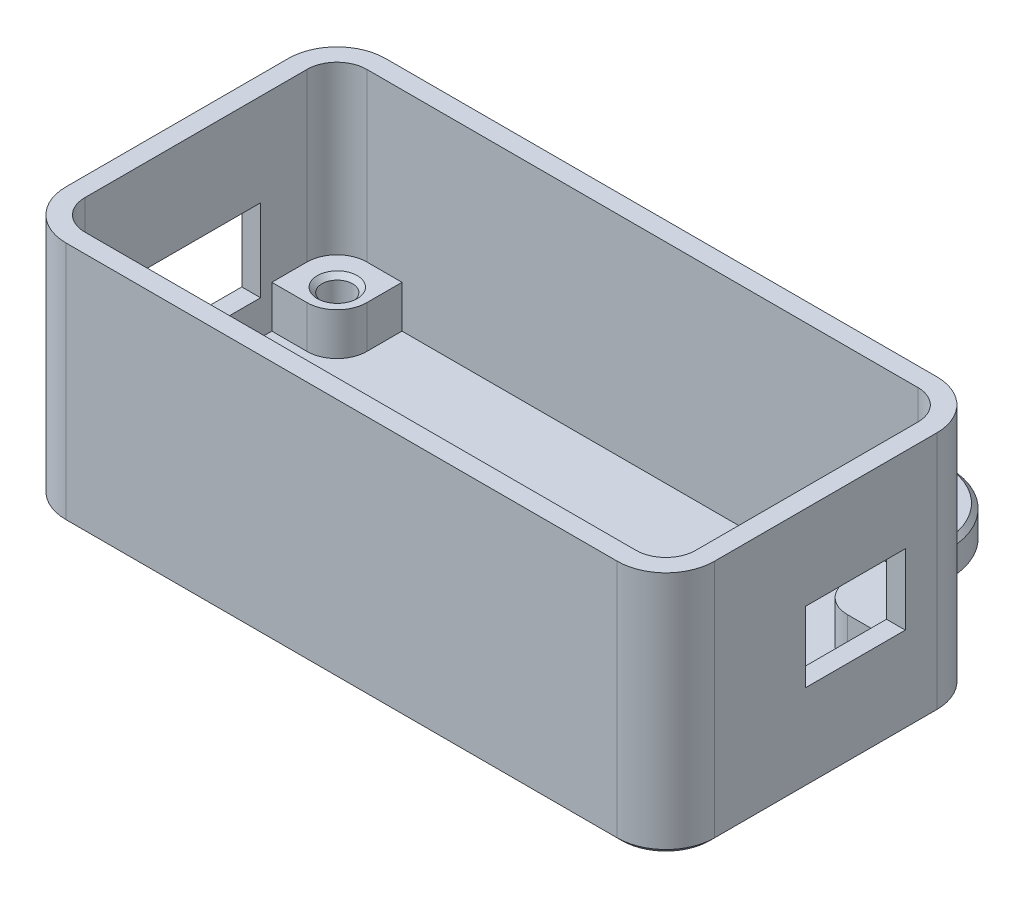
SolidWorks part; units mm, degrees
ref_plane "Front Plane" through (0, 0, 0) normal (0, 0, 1) x (1, 0, 0)
ref_plane "Top Plane" through (0, 0, 0) normal (0, 1, 0) x (1, 0, 0)
ref_plane "Right Plane" through (0, 0, 0) normal (1, 0, 0) x (0, 0, -1)
sketch "Sketch1" plane through (0, 0, 0) normal (0, 1, 0) x (1, 0, 0)
  line L0 (-23.46, 13.6) -> (23.46, 13.6)
  line L1 (-23.46, -12) -> (23.46, -12)
  line L2 (-26, -9.46) -> (-26, 9.46)
  line L3 (-23.46, 12) -> (23.46, 12)
  line L4 (26, -9.46) -> (26, 9.46)
  line L5 (27.6, -9.46) -> (27.6, 9.46)
  line L6 (-23.46, -13.6) -> (23.46, -13.6)
  line L7 (-27.6, -9.46) -> (-27.6, 9.46)
  line L8 (0, 12) -> (0, -12) construction
  line L16 (23.46, 12) -> (26, 12) construction
  line L17 (26, 12) -> (26, 9.46) construction
  arc A0 (26, -9.46) -> (23.46, -12) centre (23.46, -9.46) cw
  arc A1 (-23.46, -12) -> (-26, -9.46) centre (-23.46, -9.46) cw
  arc A2 (-26, 9.46) -> (-23.46, 12) centre (-23.46, 9.46) cw
  arc A3 (23.46, 12) -> (26, 9.46) centre (23.46, 9.46) cw
  arc A4 (23.46, 13.6) -> (27.6, 9.46) centre (23.46, 9.46) cw
  arc A5 (27.6, -9.46) -> (23.46, -13.6) centre (23.46, -9.46) cw
  arc A6 (-23.46, -13.6) -> (-27.6, -9.46) centre (-23.46, -9.46) cw
  arc A7 (-27.6, 9.46) -> (-23.46, 13.6) centre (-23.46, 9.46) cw
  point P8 (0, 12)
  point P9 (26, -12)
  point P11 (0, -12)
  point P13 (-26, -12)
  point P14 (26, 0)
  point P17 (-26, 0)
  point P19 (-26, 12)
  point P34 (0, 0)
  dimension "D3" = 2.54
  dimension "D1" = 52
  dimension "D2" = 24
  dimension "D4" = 1.6
extrude "base" add sketch "Sketch1" against normal blind 3 contours L0 A4 L5 A5 L6 A6 L7 A7
extrude "walls" add sketch "Sketch1<3>" along normal blind 17.8 contours A7 L7 A6 L6 A5 L5 A4 L0 L3 A3 L4 A0 L1 A1 L2 A2 region at (0, 0, -12.9846)
sketch "Sketch1<3>" plane through (0, 0, 0) normal (0, 1, 0) x (1, 0, 0) same geometry as "Sketch1"
sketch "Sketch2" plane through (0, 0, 0) normal (0, 1, 0) x (1, 0, 0)
  line L0 (-26, 6.46) -> (-23, 6.46)
  line L3 (-20.46, 12) -> (-20.46, 9)
  line L4 (-26, 6.46) -> (-26, 12)
  line L5 (-26, 12) -> (-20.46, 12)
  line L6 (-26, 9.46) -> (-26, 12) construction
  line L7 (-26, 12) -> (-23.46, 12) construction
  arc A0 (-23, 6.46) -> (-20.46, 9) centre (-23, 9) ccw
  point P2 (-25.6926, 12)
  dimension "D1" = 2.54
  dimension "D2" = 3
extrude "pedestal" add sketch "Sketch2" along normal blind 3.6
sketch "Sketch8" plane through (0, 3.6, 0) normal (0, 1, 0) x (1, 0, 0)
  line L0 (-22.86, 8.89) -> (0, 8.89) construction
  line L1 (0, 8.89) -> (0, 0) construction
  circle A0 centre (-22.86, 8.89) radius 1.3
  dimension "D3" = 2.6
  dimension "D1" = 8.89
  dimension "D2" = 22.86
extrude "thruhole" cut sketch "Sketch8" against normal through all
sketch "Sketch10" plane through (0, -3, 0) normal (0, -1, 0) x (1, 0, 0)
  line L1 (-25.8622, -8.89) -> (-24.3611, -11.49)
  line L2 (-24.3611, -11.49) -> (-21.3589, -11.49)
  line L3 (-21.3589, -11.49) -> (-19.8578, -8.89)
  line L4 (-19.8578, -8.89) -> (-21.3589, -6.29)
  line L5 (-21.3589, -6.29) -> (-24.3611, -6.29)
  line L6 (-24.3611, -6.29) -> (-25.8622, -8.89)
  circle A0 centre (-22.86, -8.89) radius 2.6 construction
  dimension "D1" = 5.2
extrude "nut hole" cut sketch "Sketch10" against normal blind 2.4
mirror "Mirror1" about plane through (0, 0, 0) normal (1, 0, 0) of "pedestal"
mirror "Mirror2" about plane through (0, 0, 0) normal (0, 0, 1) of "Mirror1", "pedestal"
sketch "Sketch6" plane through (0, -3, 0) normal (0, 1, 0) x (1, 0, 0)
  line L1 (-18.5, 19.6) -> (-6.5, 19.6) construction
  line L2 (-18.5, 19.6) -> (-18.5, 13.6)
  line L3 (-18.5, 13.6) -> (-6.5, 13.6)
  line L4 (-6.5, 19.6) -> (-6.5, 13.6)
  line L10 (-12.5, 13.6) -> (12.5, 13.6) construction
  line L11 (-23.46, 13.6) -> (23.46, 13.6) construction
  arc A0 (-18.5, 19.6) -> (-6.5, 19.6) centre (-12.5, 19.6) cw
  circle A1 centre (-12.5, 19.6) radius 3.05
  point P6 (-12.5, 13.6)
  point P16 (0, 13.6)
  point P17 (0, 13.6)
  dimension "D2" = 6
  dimension "D3" = 6.1
  dimension "D4" = 25
  dimension "D1" = 6
extrude "eyelet" add sketch "Sketch6" along normal blind 3
mirror "Mirror3" about plane through (0, 0, 0) normal (1, 0, 0) of "eyelet"
sketch "Sketch4" plane through (-26, 0, 0) normal (1, 0, 0) x (0, 0, -1)
  line L0 (-9.46, 3.6) -> (9.46, 3.6) construction
  line L1 (0, 3.6) -> (0, 6.44) construction
  line L3 (-5.5, 9.94) -> (5.5, 9.94)
  line L4 (-5.5, 9.94) -> (-5.5, 2.94)
  line L5 (-5.5, 2.94) -> (5.5, 2.94)
  line L6 (5.5, 9.94) -> (5.5, 2.94)
  line L7 (-5.5, 9.94) -> (5.5, 2.94) construction
  line L8 (-5.5, 2.94) -> (5.5, 9.94) construction
  dimension "D1" = 11
  dimension "D2" = 7
  dimension "D3" = 2.84
extrude "hole_USB_port" cut sketch "Sketch4" against normal through all
sketch "Sketch5" plane through (26, 0, 0) normal (-1, 0, 0) x (0, 0, 1)
  line L0 (-12, 3.6) -> (12, 3.6) construction
  line L1 (-2.53, 7.6) -> (-2.53, 3.6) construction
  line L2 (-6.78, 4.6) -> (1.72, 4.6)
  line L3 (-6.78, 4.6) -> (-6.78, 10.6)
  line L4 (-6.78, 10.6) -> (1.72, 10.6)
  line L5 (1.72, 4.6) -> (1.72, 10.6)
  line L6 (-6.78, 4.6) -> (1.72, 10.6) construction
  line L7 (-6.78, 10.6) -> (1.72, 4.6) construction
  point P4 (-2.53, 7.6)
  dimension "D1" = 8.5
  dimension "D2" = 6
  dimension "D3" = 9.47
  dimension "D4" = 4
extrude "hole_screw_term" cut sketch "Sketch5" against normal through all
ref_axis "Axis1" through (0, 18.84, 0) along (0, -1, 0)
pattern_circular "CirPattern1" count 2 over 360 about axis through (0, 18.84, 0) along (0, -1, 0) of "nut hole", "thruhole"
chamfer "Chamfer1" distance 0.4 angle 45 40 edges at (12.5, -3, -16.55) (-12.5, -3, -16.55) (-27.6, -3, 0) (-26.3874, -3, 12.3874) (0, -3, 13.6) (26.3874, -3, 12.3874) (27.6, -3, 0) (26.3874, -3, -12.3874) (20.98, -3, -13.6) (18.5, -3, -16.6) (12.5, -3, -25.6) (6.5, -3, -16.6) (0, -3, -13.6) (-6.5, -3, -16.6) (-12.5, -3, -25.6) (-18.5, -3, -16.6) (-20.98, -3, -13.6) (-26.3874, -3, -12.3874) (-25.1117, -3, -10.19) (-22.86, -3, -11.49) (-20.6083, -3, -10.19) (-20.6083, -3, -7.59) (-22.86, -3, -6.29) (-25.1117, -3, -7.59) (-22.86, 3.6, -7.59) (-18.5, 0, -16.6) (-12.5, 0, -25.6) (-6.5, 0, -16.6) (6.5, 0, -16.6) (12.5, 0, -25.6) (18.5, 0, -16.6) (-12.5, 0, -16.55) (12.5, 0, -16.55) (25.1117, -3, 10.19) (22.86, -3, 11.49) (20.6083, -3, 10.19) (20.6083, -3, 7.59) (22.86, -3, 6.29) (25.1117, -3, 7.59) (22.86, 3.6, 7.59)
